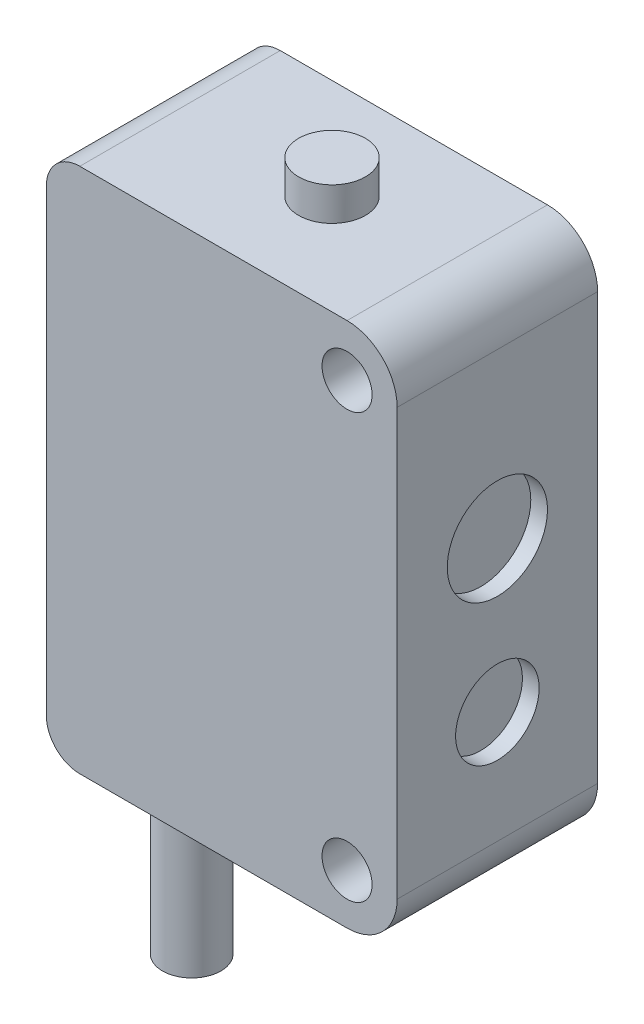
SolidWorks part; units mm, degrees
ref_plane "Plan de face" through (0, 0, 0) normal (0, 0, 1) x (1, 0, 0)
ref_plane "Plan de dessus" through (0, 0, 0) normal (0, 1, 0) x (1, 0, 0)
ref_plane "Plan de droite" through (0, 0, 0) normal (1, 0, 0) x (0, 0, -1)
sketch "Esquisse1" plane through (0, 0, 0) normal (0, 0, 1) x (1, 0, 0)
  line L1 (0, 0) -> (21, 0)
  line L2 (0, 0) -> (0, 31.5)
  line L3 (0, 31.5) -> (21, 31.5)
  line L4 (21, 0) -> (21, 31.5)
  circle A0 centre (18, 28.4) radius 1.5
  circle A1 centre (18, 3) radius 1.5
  point P0 (21, 31.1759)
  point P3 (21, 0)
  point P11 (21, 0)
  point P14 (21, 31.5)
  point P17 (0, 0)
  point P20 (0, 0)
  point P21 (21, 0.3265)
  dimension "D3" = 3
  dimension "D4" = 3
  dimension "D1" = 31.5
  dimension "D2" = 21
  dimension "D5" = 25.4
  dimension "D6" = 3
  dimension "D7" = 3
extrude "Boss.-Extru.1" add sketch "Esquisse1" along normal blind 12
sketch "Esquisse3" plane through (0, 0, 0) normal (0, -1, 0) x (1, 0, 0)
  line L0 (21, 12) -> (21, 0) construction
  line L2 (0, 6) -> (21, 6) construction
  line L3 (0, 12) -> (0, 0) construction
  circle A0 centre (2.7, 6) radius 1.75
  point P4 (21, 6)
  point P5 (0, 0)
  dimension "D1" = 3.5
  dimension "D2" = 18.3
extrude "Boss.-Extru.2" add sketch "Esquisse3" along normal blind 12
sketch "Esquisse4" plane through (21, 0, 0) normal (1, 0, 0) x (0, 0, -1)
  line L0 (-6, 31.5) -> (-6, 0) construction
  line L1 (-12, 31.5) -> (0, 31.5) construction
  line L2 (-12, 0) -> (0, 0) construction
  circle A0 centre (-6, 9.7) radius 2.5
  circle A1 centre (-6, 18.7) radius 3
  point P10 (-6, 7.0485)
  point P11 (-6, 20.0245)
  dimension "D1" = 6
  dimension "D2" = 5
  dimension "D3" = 9
  dimension "D4" = 9.7
extrude "Enlèv. mat.-Extru.1" cut sketch "Esquisse4" against normal blind 1
sketch "Esquisse5" plane through (0, 31.5, 0) normal (0, 1, 0) x (1, 0, 0)
  line L0 (0, -6) -> (21, -6) construction
  line L1 (0, -12) -> (0, 0) construction
  line L2 (21, -12) -> (21, 0) construction
  circle A0 centre (11.1, -6) radius 2
  dimension "D1" = 4
  dimension "D2" = 9.9
extrude "Boss.-Extru.3" add sketch "Esquisse5" along normal blind 2
fillet "Congé1" radius 3 2 edges at (21, 0, 6) (21, 31.5, 6)
fillet "Congé2" radius 2 2 edges at (0, 0, 6) (0, 31.5, 6)
